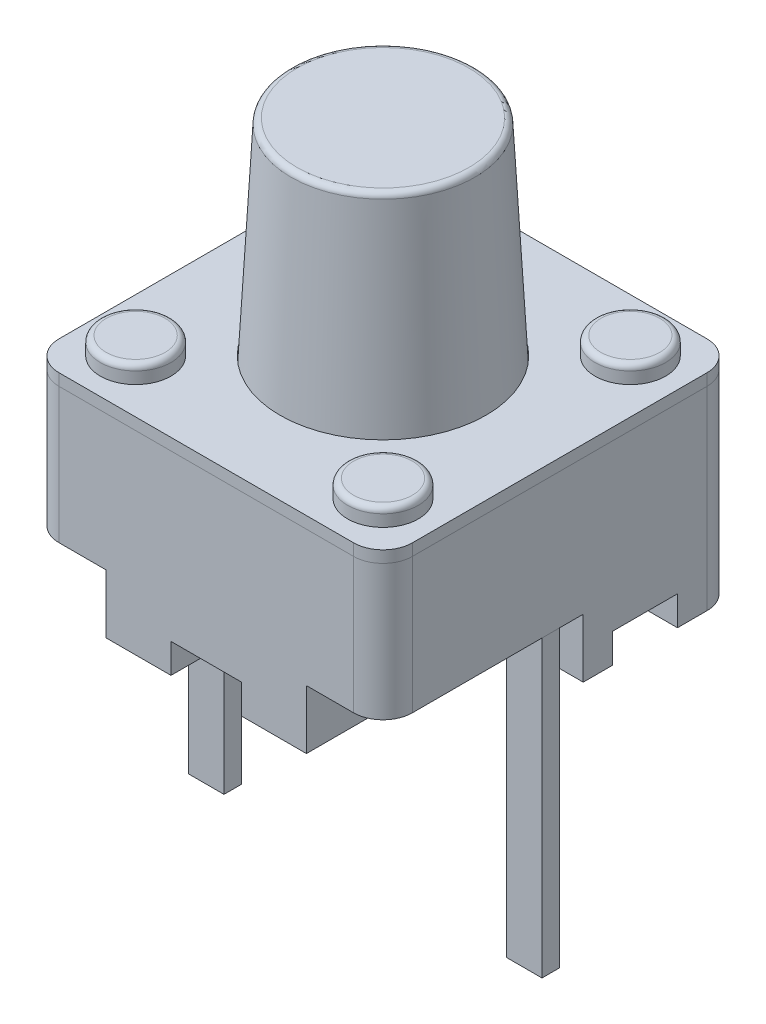
SolidWorks part; units mm, degrees
material "Custom Plastic"
ref_plane "Front Plane" through (0, 0, 0) normal (0, 0, 1) x (1, 0, 0)
ref_plane "Top Plane" through (0, 0, 0) normal (0, 1, 0) x (1, 0, 0)
ref_plane "Right Plane" through (0, 0, 0) normal (1, 0, 0) x (0, 0, -1)
sketch "Sketch1" plane through (0, 0, 0) normal (0, 1, 0) x (1, 0, 0)
  line L0 (-3.2652, 0) -> (3.207, 0) construction
  line L1 (-2.5, 3) -> (2.5, 3)
  line L2 (-3, 2.5) -> (-3, -2.5)
  line L3 (-2.5, -3) -> (2.5, -3)
  line L4 (3, 2.5) -> (3, -2.5)
  line L5 (-3, 3) -> (3, -3) construction
  line L6 (-3, -3) -> (3, 3) construction
  line L7 (0, -3.1905) -> (0, 3.2124) construction
  line L8 (3, 0) -> (2.4, 0)
  line L9 (3, 0) -> (3, -0.3)
  line L10 (3, -0.3) -> (2.4, -0.3)
  line L11 (2.4, 0) -> (2.4, -0.3)
  line L12 (-3, -0.3) -> (-2.4, -0.3)
  line L13 (-2.4, 0) -> (-2.4, -0.3)
  line L14 (-3, 0) -> (-2.4, 0)
  circle A0 centre (2.1, 2.1) radius 0.6
  circle A1 centre (2.1, -2.1) radius 0.6
  circle A2 centre (-2.1, -2.1) radius 0.6
  circle A3 centre (-2.1, 2.1) radius 0.6
  circle A4 centre (0, 0) radius 1.75
  arc A5 (2.5, 3) -> (3, 2.5) centre (2.5, 2.5) cw
  arc A6 (2.5, -3) -> (3, -2.5) centre (2.5, -2.5) ccw
  arc A7 (-3, -2.5) -> (-2.5, -3) centre (-2.5, -2.5) ccw
  arc A8 (-2.5, 3) -> (-3, 2.5) centre (-2.5, 2.5) ccw
  point P0 (0, 0)
  point P1 (0, 0)
  point P9 (0, 0)
  point P18 (0, 0)
  dimension "D1" = 6
  dimension "D2" = 0.9
  dimension "D3" = 1.2
  dimension "D5" = 3.5
  dimension "D6" = 0.5
  dimension "D7" = 0.6
  dimension "D8" = 0.3
  dimension "D4" = 4
extrude "Base" add sketch "Sketch1" along normal blind 3.3 contours L14 L2 L12 L13 | L1 A8 L2 L14 L13 L12 A7 L3 A6 L4 L10 L11 L8 A5 A0 A1 A2 A3 A4 | A3 | A2 | A4 | A1 | L8 L11 L10 L4 | A0 region at (0, 0, -2.9151) region at (-2.7, 0, 0.15) region at (2.7, 0, 0.15) region at (2.1, 0, -2.1) region at (2.1, 0, 2.1) region at (-2.1, 0, 2.1) region at (-2.1, 0, -2.1) region at (0, 0, 0)
extrude "Top Plate" add sketch "Sketch1<3>" along normal blind 0.2 from surface separate body contours L1 A8 L2 L14 L13 L12 A7 L3 A6 L4 L10 L11 L8 A5 A0 A1 A2 A3 A4 | L8 L11 L10 L4 | L14 L2 L12 L13 region at (0, 0, -2.9151) region at (-2.7, 0, 0.15) region at (2.7, 0, 0.15) starting at face at (0, 3.3, 0)
sketch "Sketch1<3>" plane through (0, 0, 0) normal (0, 1, 0) x (1, 0, 0) same geometry as "Sketch1"
extrude "Knobs" add sketch "Sketch1<4>" along normal blind 0.5 from offset 3.3 contours A1 | A2 | A3 | A0 region at (2.1, 0, -2.1) region at (2.1, 0, 2.1) region at (-2.1, 0, 2.1) region at (-2.1, 0, -2.1)
sketch "Sketch1<4>" plane through (0, 0, 0) normal (0, 1, 0) x (1, 0, 0) same geometry as "Sketch1"
extrude "Actuator" add sketch "Sketch1<5>" along normal blind 3.7 draft 3 from surface separate body contours A4 region at (0, 0, 0) starting at face at (-2.1, 3.3, -1.5)
sketch "Sketch1<5>" plane through (0, 0, 0) normal (0, 1, 0) x (1, 0, 0) same geometry as "Sketch1"
sketch "Sketch2" plane through (0, 0, 0) normal (0, -1, 0) x (1, 0, 0)
  line L0 (0, 3) -> (0.6, 3)
  line L1 (0, 3) -> (0, -3) construction
  line L2 (-2.5, 3) -> (2.5, 3) construction
  line L3 (0.6, 3) -> (1.7, 3)
  line L4 (0, -3) -> (0.6, -3)
  line L5 (-1.7, -2) -> (-3, -2)
  line L6 (0.6, -3) -> (0.6, 3)
  line L7 (-1.7, -0.9) -> (-1.7, -2)
  line L8 (-1.7, -0.9) -> (-3, -0.9)
  line L9 (1.7, -0.9) -> (3, -0.9)
  line L10 (1.7, -0.9) -> (1.7, -2)
  line L11 (-3, -0.4) -> (-1.7, -0.4)
  line L12 (-0.6, -3) -> (-0.6, 3)
  line L13 (1.7, 3) -> (1.7, -0.4)
  line L14 (-1.7, 3) -> (-1.7, -0.4)
  line L15 (3, 0) -> (-3, 0) construction
  line L16 (-3, -2.5) -> (-3, 2.5) construction
  line L21 (-2.5, -3) -> (2.5, -3) construction
  line L22 (1.7, -2) -> (3, -2)
  line L23 (3, -2.5) -> (3, 2.5) construction
  line L25 (3, -0.4) -> (1.7, -0.4)
  point P5 (0, 0)
  point P12 (0, 0)
  arc M1 (3, 2.5) -> (2.5, 3) centre (2.5, 2.5) ccw
  line M2 (2.5, 3) -> (-2.5, 3)
  arc M3 (-2.5, 3) -> (-3, 2.5) centre (-2.5, 2.5) ccw
  line M4 (-3, 2.5) -> (-3, -2.5)
  line M6 (-2.5, -3) -> (2.5, -3)
  line M8 (3, -2.5) -> (3, 2.5)
  dimension "D1" = 0.6
  dimension "D2" = 1.7
  dimension "D3" = 0.4
  dimension "D4" = 1
  dimension "D6" = 0.5
extrude "Base Leg Cutout" cut sketch "Sketch2" against normal blind 1 from surface contours L14 L11 M2 M3 M4 | L25 L13 M8 M1 M2 region at (2.3434, 0, 1.2805) region at (-2.3434, 0, 1.2805) starting at face at (0, 0, 0)
extrude "Base Shallow Cutout" cut sketch "Sketch2<3>" against normal blind 0.5 contours L1 L12 M2 M6 | L10 L22 L9 M8 | L7 L8 L5 M4 region at (2.35, 0, -1.45) region at (-2.35, 0, -1.45) region at (0, 0, 0)
sketch "Sketch2<3>" plane through (0, 0, 0) normal (0, -1, 0) x (1, 0, 0) same geometry as "Sketch2"
extrude "Pins" add sketch "Sketch1<7>" against normal blind 5 from offset 1 separate body contours L14 L2 L12 L13 | L8 L11 L10 L4 region at (-2.7, 0, 0.15) region at (2.7, 0, 0.15)
sketch "Sketch1<7>" plane through (0, 0, 0) normal (0, 1, 0) x (1, 0, 0) same geometry as "Sketch1"
fillet "Fillet1" radius 0.1 1 edges at (0, 7, 1.5561)
fillet "Fillet2" radius 0.1 4 edges at (-2.1, 3.8, -1.5) (2.1, 3.8, -1.5) (-2.1, 3.8, 2.7) (2.1, 3.8, 2.7)
